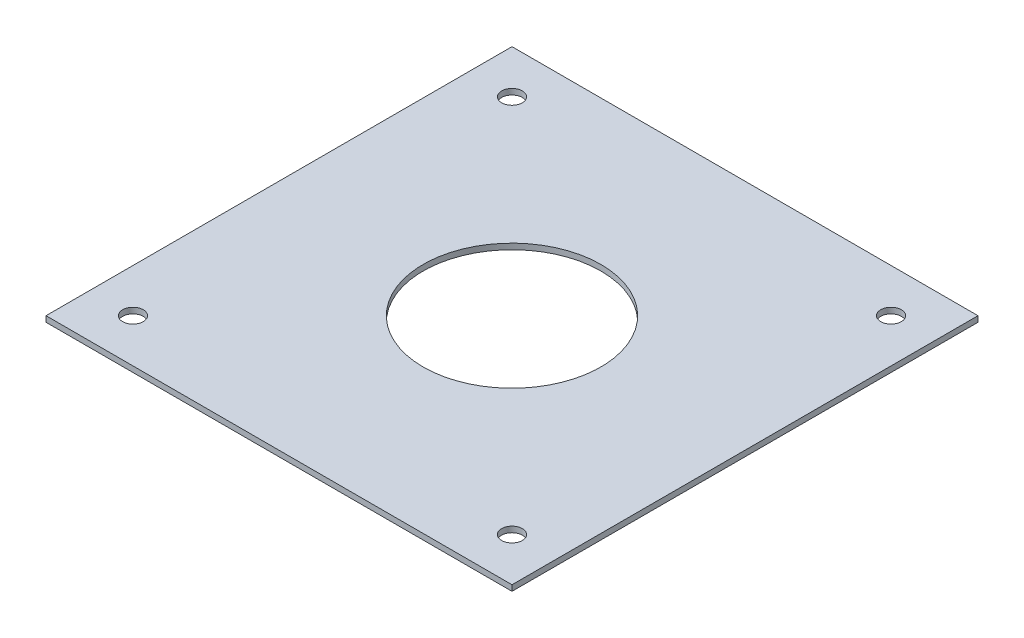
SolidWorks part; units mm, degrees
material "1060 Alloy"
ref_plane "Front Plane" through (0, 0, 0) normal (0, 0, 1) x (1, 0, 0)
ref_plane "Top Plane" through (0, 0, 0) normal (0, 1, 0) x (1, 0, 0)
ref_plane "Right Plane" through (0, 0, 0) normal (1, 0, 0) x (0, 0, -1)
sketch "Sketch1" plane through (0, 0, 0) normal (0, 0, 1) x (1, 0, 0)
  line L0 (0, 0) -> (406.4, 0)
  dimension "D1" = 406.4
base flange "Base-Flange1" sketch "Sketch1" end condition blind depth 406.4 reverse direction no thickness 5 reverse thickness direction no bend radius 1
sketch "Bend-Lines1" plane through (0, 0, 0) normal (0, 1, 0) x (1, 0, 0)
sketch "Bounding-Box1" plane through (0, 0, 0) normal (0, 1, 0) x (1, 0, 0)
sketch "Sketch6" plane through (0, 0, 0) normal (0, 1, 0) x (1, 0, 0)
  line L0 (406.4, 0) -> (0, -406.4)
  line L1 (0, 0) -> (406.4, -406.4)
  line L2 (406.4, 0) -> (368.4849, -37.9151)
  line L3 (0, 0) -> (37.9151, -37.9151)
  line L4 (406.4, 0) -> (0, 0)
  line L5 (0, 0) -> (0, -406.4)
  line L6 (0, -406.4) -> (406.4, -406.4)
  line L7 (406.4, -406.4) -> (406.4, 0)
  line L8 (406.4, 0) -> (0, 0)
  line L9 (0, 0) -> (0, -406.4)
  line L10 (0, -406.4) -> (406.4, -406.4)
  line L11 (406.4, -406.4) -> (406.4, 0)
  line L12 (406.4, -406.4) -> (368.4849, -368.4849)
  line L13 (0, -406.4) -> (37.9151, -368.4849)
  circle A0 centre (203.2, -203.2) radius 77.5
  circle A1 centre (368.4849, -37.9151) radius 9
  circle A2 centre (37.9151, -37.9151) radius 9
  circle A3 centre (368.4849, -368.4849) radius 9
  circle A4 centre (37.9151, -368.4849) radius 9
  dimension "D2" = 155
  dimension "D4" = 18
  dimension "D8" = 18
  dimension "D9" = 18
  dimension "D10" = 18
  dimension "D3" = 53.62
  dimension "D5" = 53.62
  dimension "D6" = 53.62
  dimension "D7" = 53.62
  dimension "D1" = 0
extrude "Cut-Extrude1" cut sketch "Sketch6" against normal through all contours L1 A2 L3 | L3 A2 L1 | L2 A1 L0 | L0 A1 L2 | L1 A3 | L1 A3 | L0 A4 | L0 A4 region at (371.1859, 0, 40.616) region at (365.784, 0, 35.2141) region at (40.616, 0, 35.2141) region at (35.2141, 0, 40.616) region at (365.784, 0, 371.1859) region at (371.1859, 0, 365.784) region at (35.2141, 0, 365.784) region at (40.616, 0, 371.1859)
extrude "Cut-Extrude2" cut sketch "Sketch6<4>" against normal blind 10 contours L1 A0 L0 | L0 A0 L1 | L1 A0 L0 | L0 A0 L1 region at (249.7163, 0, 203.2) region at (203.2, 0, 156.6837) region at (203.2, 0, 249.7163) region at (156.6837, 0, 203.2)
sketch "Sketch6<4>" plane through (0, 0, 0) normal (0, 1, 0) x (1, 0, 0) same geometry as "Sketch6"
sheet metal parameters "Sheet-Metal1" thickness 5 parameters "D1"=1
flat pattern "Flat-Pattern1"
sketch "Bend-Lines2" plane through (0, 0, 0) normal (0, 1, 0) x (1, 0, 0)
sketch3d "Bounding-Box2"
  line L0 (0, 406.4, 0) -> (0, 0, 0) construction
  line L1 (406.4, 406.4, 0) -> (406.4, 0, 0) construction
  line L2 (0, 406.4, 0) -> (406.4, 406.4, 0) construction
  line L3 (0, 0, 0) -> (406.4, 0, 0) construction
equation "\"a\"= 53.62"
equation "\"D5@Sketch6\"=\"a\""
equation "\"D3@Sketch6\"=\"a\""
equation "\"D6@Sketch6\"=\"a\""
equation "\"D7@Sketch6\"=\"a\""
equation "\"b\"= 18"
equation "\"D4@Sketch6\"=\"b\""
equation "\"D8@Sketch6\"=\"b\""
equation "\"D9@Sketch6\"=\"b\""
equation "\"D10@Sketch6\"=\"b\""
